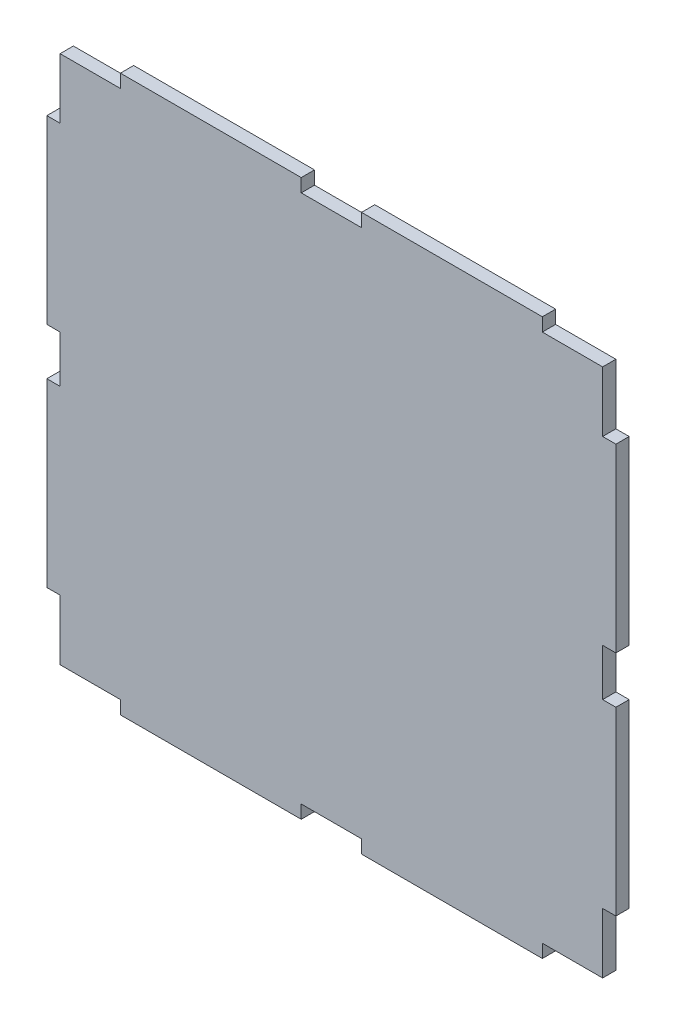
SolidWorks part; units mm, degrees
ref_plane "Front Plane" through (0, 0, 0) normal (0, 0, 1) x (1, 0, 0)
ref_plane "Top Plane" through (0, 0, 0) normal (0, 1, 0) x (1, 0, 0)
ref_plane "Right Plane" through (0, 0, 0) normal (1, 0, 0) x (0, 0, -1)
sketch "Sketch5" plane through (0, 0, 0) normal (0, 0, 1) x (1, 0, 0)
  line L0 (259.6128, -168.5164) -> (259.6128, -391.5284) construction
  line L1 (145.3128, -168.5164) -> (373.9128, -168.5164)
  line L2 (145.3128, -168.5164) -> (145.3128, -391.5284)
  line L3 (145.3128, -391.5284) -> (373.9128, -391.5284)
  line L4 (373.9128, -168.5164) -> (373.9128, -391.5284)
  line L5 (170.7128, -168.5164) -> (246.9128, -168.5164)
  line L6 (170.7128, -168.5164) -> (170.7128, -162.9284)
  line L7 (170.7128, -162.9284) -> (246.9128, -162.9284)
  line L8 (246.9128, -168.5164) -> (246.9128, -162.9284)
  line L9 (139.7248, -193.9164) -> (145.3128, -193.9164)
  line L10 (139.7248, -193.9164) -> (139.7248, -270.1164)
  line L11 (139.7248, -270.1164) -> (145.3128, -270.1164)
  line L12 (145.3128, -193.9164) -> (145.3128, -270.1164)
  line L13 (145.3128, -280.0224) -> (373.9128, -280.0224) construction
  line L14 (272.3128, -168.5164) -> (272.3128, -162.9284)
  line L15 (348.5128, -162.9284) -> (272.3128, -162.9284)
  line L16 (348.5128, -168.5164) -> (348.5128, -162.9284)
  line L17 (348.5128, -391.5284) -> (348.5128, -397.1164)
  line L18 (348.5128, -397.1164) -> (272.3128, -397.1164)
  line L19 (272.3128, -391.5284) -> (272.3128, -397.1164)
  line L20 (246.9128, -391.5284) -> (246.9128, -397.1164)
  line L21 (170.7128, -397.1164) -> (246.9128, -397.1164)
  line L22 (170.7128, -391.5284) -> (170.7128, -397.1164)
  line L23 (139.7248, -289.9284) -> (145.3128, -289.9284)
  line L24 (139.7248, -366.1284) -> (139.7248, -289.9284)
  line L25 (139.7248, -366.1284) -> (145.3128, -366.1284)
  line L26 (379.5008, -366.1284) -> (373.9128, -366.1284)
  line L27 (379.5008, -366.1284) -> (379.5008, -289.9284)
  line L28 (379.5008, -289.9284) -> (373.9128, -289.9284)
  line L29 (379.5008, -270.1164) -> (373.9128, -270.1164)
  line L30 (379.5008, -193.9164) -> (379.5008, -270.1164)
  line L31 (379.5008, -193.9164) -> (373.9128, -193.9164)
  dimension "D1" = 223.012
  dimension "D2" = 228.6
  dimension "D3" = 76.2
  dimension "D4" = 5.588
  dimension "D5" = 25.4
  dimension "D6" = 25.4
extrude "Boss-Extrude1" add sketch "Sketch5" along normal blind 5.588 contours L24 L25 L2 L23 | L3 L22 L21 L20 | L3 L19 L18 L17 | L27 L28 L4 L26 | L1 L16 L15 L14 | L30 L31 L4 L29 | L1 L8 L7 L6 | L10 L11 L2 L9 | L2 L3 L4 L1 region at (208.8128, -165.7224, 0) region at (142.5188, -232.0164, 0) region at (310.4128, -165.7224, 0) region at (142.5188, -328.0284, 0) region at (376.7068, -232.0164, 0) region at (208.8128, -394.3224, 0) region at (376.7068, -328.0284, 0) region at (310.4128, -394.3224, 0)
equation "\"width\"= 9in"
equation "\"Height\"= 18in"
equation "\"thick\"= 0.22"
equation "\"D1@Sketch5\"= \"width\" - \"thick\""
equation "\"D2@Sketch5\" = \"width\""
equation "\"D4@Sketch5\"=\"thick\""
equation "\"D1@Boss-Extrude1\"=\"thick\""
